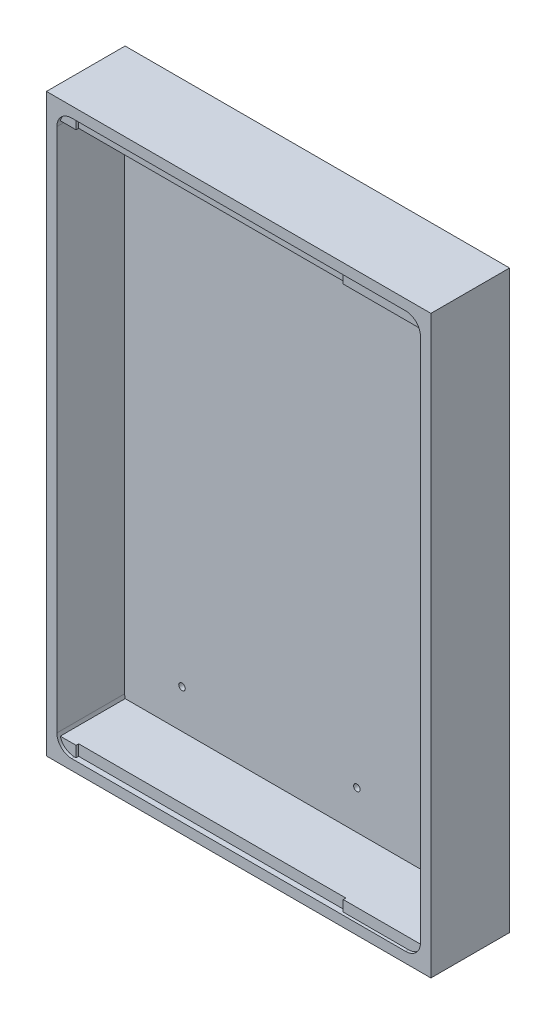
SolidWorks part; units mm, degrees
ref_plane "Front Plane" through (0, 0, 0) normal (0, 0, 1) x (1, 0, 0)
ref_plane "Top Plane" through (0, 0, 0) normal (0, 1, 0) x (1, 0, 0)
ref_plane "Right Plane" through (0, 0, 0) normal (1, 0, 0) x (0, 0, -1)
sketch "Sketch1" plane through (0, 0, 0) normal (0, 0, 1) x (1, 0, 0)
  line L1 (-88.5, -132.5) -> (88.5, -132.5)
  line L2 (-88.5, -132.5) -> (-88.5, 132.5)
  line L3 (-88.5, 132.5) -> (88.5, 132.5)
  line L4 (88.5, -132.5) -> (88.5, 132.5)
  line L5 (-88.5, -132.5) -> (88.5, 132.5) construction
  line L6 (-88.5, 132.5) -> (88.5, -132.5) construction
  circle A0 centre (-57.3, -104.9) radius 1.5 construction
  circle A1 centre (23.21, -104.9) radius 1.5 construction
  circle A2 centre (23.21, 104.9) radius 1.5 construction
  circle A3 centre (-57.3, 104.9) radius 1.5 construction
  circle A4 centre (-57.3, -104.9) radius 1.5
  circle A5 centre (23.21, -104.9) radius 1.5
  circle A6 centre (23.21, 104.9) radius 1.5
  circle A7 centre (-57.3, 104.9) radius 1.5
  point P0 (0, 0)
  dimension "D1" = 177
  dimension "D2" = 265
extrude "Boss-Extrude1" add sketch "Sketch1" along normal blind 5
sketch "Sketch2" plane through (0, 0, 5) normal (0, 0, 1) x (1, 0, 0)
  line L0 (83.7, -127.7) -> (83.7, 127.7)
  line L1 (83.7, 127.7) -> (-83.7, 127.7)
  line L2 (-83.7, 127.7) -> (-83.7, -127.7)
  line L3 (-83.7, -127.7) -> (83.7, -127.7)
  line L4 (88.5, -132.5) -> (88.5, 132.5)
  line L5 (88.5, 132.5) -> (-88.5, 132.5)
  line L6 (-88.5, 132.5) -> (-88.5, -132.5)
  line L7 (-88.5, -132.5) -> (88.5, -132.5)
  line L8 (88.5, -132.5) -> (88.5, 132.5)
  line L9 (88.5, 132.5) -> (-88.5, 132.5)
  line L10 (-88.5, 132.5) -> (-88.5, -132.5)
  line L11 (-88.5, -132.5) -> (88.5, -132.5)
  dimension "D1" = 0
  dimension "D2" = 4.8
extrude "Boss-Extrude2" add sketch "Sketch2" along normal blind 31.2
fillet "Fillet1" radius 6.82 4 edges at (83.7, 127.7, 20.6) (83.7, -127.7, 20.6) (-83.7, -127.7, 20.6) (-83.7, 127.7, 20.6)
sketch "Sketch4" plane through (0, 0, 5) normal (0, 0, 1) x (1, 0, 0)
  line L0 (-83.7, 122.7) -> (83.7, 122.7)
  line L1 (-83.7, -122.7) -> (83.7, -122.7)
  line L4 (83.7, -120.88) -> (83.7, 120.88)
  line L5 (76.88, 127.7) -> (-76.88, 127.7)
  line L6 (-83.7, 120.88) -> (-83.7, -120.88)
  line L7 (-76.88, -127.7) -> (76.88, -127.7)
  line L8 (83.7, -120.88) -> (83.7, 120.88)
  line L9 (76.88, 127.7) -> (-76.88, 127.7)
  line L10 (-83.7, 120.88) -> (-83.7, -120.88)
  line L11 (-76.88, -127.7) -> (76.88, -127.7)
  arc A4 (83.7, 120.88) -> (76.88, 127.7) centre (76.88, 120.88) ccw
  arc A5 (-76.88, 127.7) -> (-83.7, 120.88) centre (-76.88, 120.88) ccw
  arc A6 (-83.7, -120.88) -> (-76.88, -127.7) centre (-76.88, -120.88) ccw
  arc A7 (76.88, -127.7) -> (83.7, -120.88) centre (76.88, -120.88) ccw
  arc A8 (83.7, 120.88) -> (76.88, 127.7) centre (76.88, 120.88) ccw
  arc A9 (-76.88, 127.7) -> (-83.7, 120.88) centre (-76.88, 120.88) ccw
  arc A10 (-83.7, -120.88) -> (-76.88, -127.7) centre (-76.88, -120.88) ccw
  arc A11 (76.88, -127.7) -> (83.7, -120.88) centre (76.88, -120.88) ccw
  arc M12 (83.7, 120.88) -> (76.88, 127.7) centre (76.88, 120.88) ccw
  line M13 (76.88, 127.7) -> (-76.88, 127.7)
  arc M14 (-76.88, 127.7) -> (-83.7, 120.88) centre (-76.88, 120.88) ccw
  arc M16 (-83.7, -120.88) -> (-76.88, -127.7) centre (-76.88, -120.88) ccw
  line M17 (-76.88, -127.7) -> (76.88, -127.7)
  arc M18 (76.88, -127.7) -> (83.7, -120.88) centre (76.88, -120.88) ccw
  dimension "D2" = 5
  dimension "D3" = 5
  dimension "D1" = 0
extrude "Boss-Extrude3" add sketch "Sketch4" along normal offset from surface (29.9 mm away) 1.3 contours L1 M16 M17 M18 | L0 M14 M12 M13 region at (0, 125.1751, 5) region at (0, -125.1751, 5) up to face at (0, 0, 36.2)
sketch "Sketch5" plane through (0, 0, 34.9) normal (0, 0, 1) x (1, 0, 0)
  line L0 (83.4527, -122.7) -> (-83.4527, -122.7) construction
  line L1 (-76.88, -127.7) -> (76.88, -127.7) construction
  line L2 (76.88, 127.7) -> (-76.88, 127.7) construction
  line L3 (-83.4527, 122.7) -> (83.4527, 122.7) construction
  line L4 (83.4527, -122.7) -> (-83.4527, -122.7)
  line L5 (-76.88, -127.7) -> (76.88, -127.7)
  line L6 (76.88, 127.7) -> (-76.88, 127.7)
  line L7 (-83.4527, 122.7) -> (83.4527, 122.7)
  line L9 (-76.16, 127.7) -> (46.84, 127.7)
  line L10 (-76.16, 127.7) -> (-76.16, -127.7)
  line L11 (-76.16, -127.7) -> (46.84, -127.7)
  line L12 (46.84, 127.7) -> (46.84, -127.7)
  line L13 (-83.7, 120.88) -> (-83.7, -120.88) construction
  arc A0 (-83.4527, -122.7) -> (-76.88, -127.7) centre (-76.88, -120.88) ccw construction
  arc A1 (76.88, -127.7) -> (83.4527, -122.7) centre (76.88, -120.88) ccw construction
  arc A2 (-76.88, 127.7) -> (-83.4527, 122.7) centre (-76.88, 120.88) ccw construction
  arc A3 (83.4527, 122.7) -> (76.88, 127.7) centre (76.88, 120.88) ccw construction
  arc A4 (-83.4527, -122.7) -> (-76.88, -127.7) centre (-76.88, -120.88) ccw
  arc A5 (76.88, -127.7) -> (83.4527, -122.7) centre (76.88, -120.88) ccw
  arc A6 (-76.88, 127.7) -> (-83.4527, 122.7) centre (-76.88, 120.88) ccw
  arc A7 (83.4527, 122.7) -> (76.88, 127.7) centre (76.88, 120.88) ccw
  dimension "D1" = 7.54
  dimension "D2" = 123
extrude "Cut-Extrude1" cut sketch "Sketch5" against normal blind 1.2 contours L12 L4 L10 L5 | L12 L6 L10 L7 region at (-14.66, -125.2, 34.9) region at (-14.66, 125.2, 34.9)
